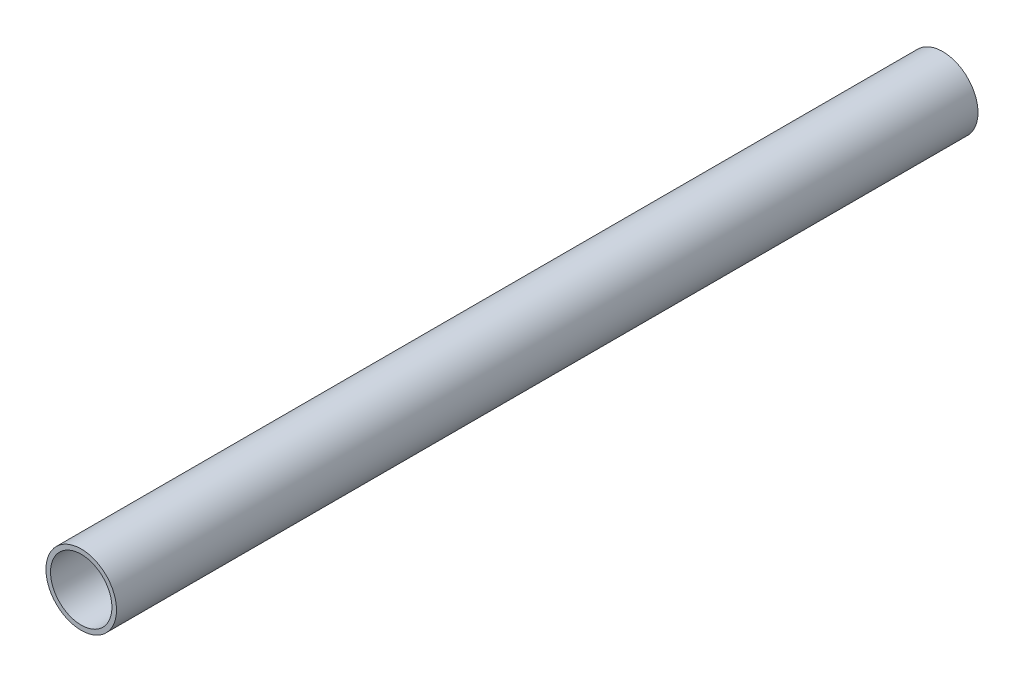
SolidWorks part; units mm, degrees
material "PVC Rigid"
ref_plane "Front Plane" through (0, 0, 0) normal (0, 0, 1) x (1, 0, 0)
ref_plane "Top Plane" through (0, 0, 0) normal (0, 1, 0) x (1, 0, 0)
ref_plane "Right Plane" through (0, 0, 0) normal (1, 0, 0) x (0, 0, -1)
sketch "Sketch1" plane through (0, 0, 0) normal (0, 0, 1) x (1, 0, 0)
  circle A0 centre (0, 0) radius 26.2509
  circle A1 centre (0, 0) radius 30.1625
  dimension "D1" = 60.325
  dimension "D2" = 3.9116
extrude "Boss-Extrude1" add sketch "Sketch1" along normal blind 736.6
